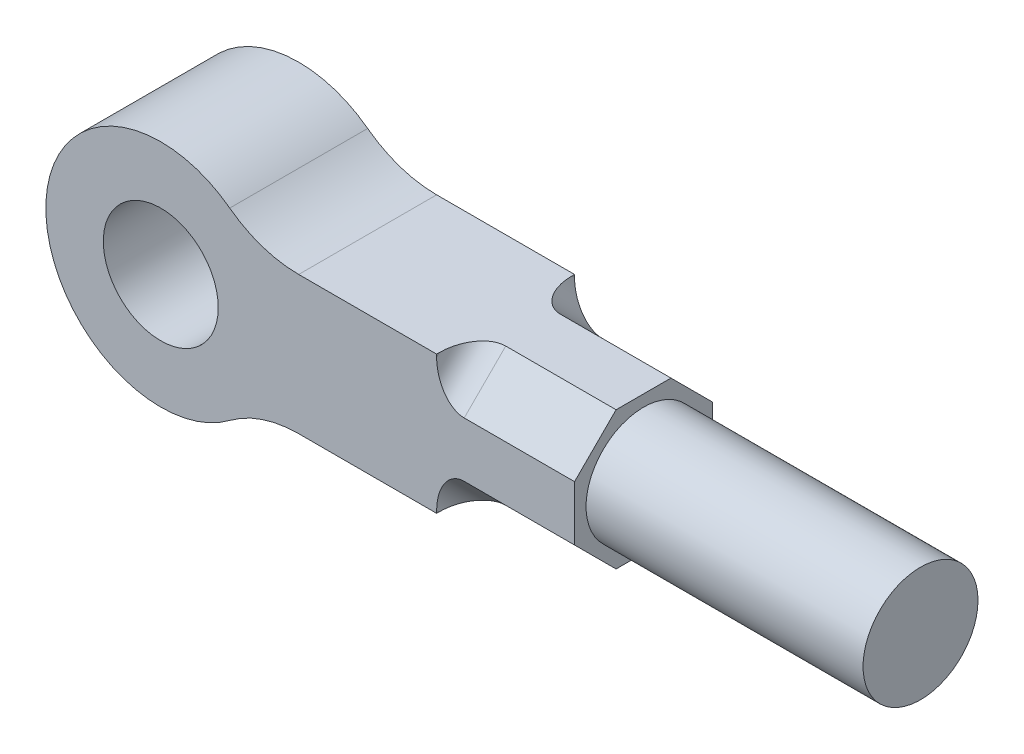
SolidWorks part; units mm, degrees
ref_plane "Front Plane" through (0, 0, 0) normal (0, 0, 1) x (1, 0, 0)
ref_plane "Top Plane" through (0, 0, 0) normal (0, 1, 0) x (1, 0, 0)
ref_plane "Right Plane" through (0, 0, 0) normal (1, 0, 0) x (0, 0, -1)
sketch "Sketch1" plane through (0, 0, 0) normal (0, 0, 1) x (1, 0, 0)
  line L0 (0, 0) -> (1046.6369, 0) construction
  line L2 (600, 300) -> (1800, 300)
  line L4 (600, -300) -> (1800, -300)
  line L5 (1800, 300) -> (1800, -300)
  arc A0 (300, 400) -> (300, -400) centre (0, 0) ccw
  circle A1 centre (0, 0) radius 250
  arc A2 (300, -400) -> (600, -300) centre (600, -800) cw
  arc A3 (300, 400) -> (600, 300) centre (600, 800) ccw
  dimension "D1" = 1000
  dimension "D2" = 500
  dimension "D4" = 500
  dimension "D3" = 600
extrude "Boss-Extrude1" add sketch "Sketch1" along normal blind 600
sketch "Sketch2" plane through (1800, 0, 0) normal (1, 0, 0) x (0, 0, -1)
  line L0 (-180.6, 300) -> (0, 119.4)
  line L1 (-600, 300) -> (0, 300) construction
  line L2 (0, -300) -> (0, 300) construction
  line L3 (0, 119.4) -> (0, 300)
  line L4 (0, 300) -> (0, 400) construction
  line L5 (0, 300) -> (-180.6, 300)
  line L6 (0, -119.4) -> (-180.6, -300)
  line L7 (-180.6, -300) -> (0, -300)
  line L8 (0, -300) -> (0, -119.4)
  line L9 (-419.4, -300) -> (-600, -119.4)
  line L10 (-600, -119.4) -> (-600, -300)
  line L11 (-600, -300) -> (-419.4, -300)
  line L12 (-600, 119.4) -> (-419.4, 300)
  line L13 (-419.4, 300) -> (-600, 300)
  line L14 (-600, 300) -> (-600, 119.4)
  circle A0 centre (-300, 0) radius 250
  point P24 (-300, 0)
  line M5 (0, -300) -> (0, 300)
  line M6 (0, 300) -> (-600, 300)
  line M7 (-600, 300) -> (-600, -300)
  line M8 (-600, -300) -> (0, -300)
  dimension "D1" = 500
  dimension "D2" = 300
  dimension "D3" = 180.6
  dimension "D4" = 180.6
  dimension "D5" = 4
extrude "Cut-Extrude1" cut sketch "Sketch2" against normal blind 600 contours L12 M7 M6 | L0 M6 M5 | L6 M5 M8 | L9 M8 M7 region at (1800, 239.8, 60.2) region at (1800, 239.8, 539.8) region at (1800, -239.8, 60.2) region at (1800, -239.8, 539.8)
extrude "Boss-Extrude2" add sketch "Sketch2<5>" along normal blind 1205 contours A0 region at (1800, 0, 300)
sketch "Sketch2<5>" plane through (1800, 0, 0) normal (1, 0, 0) x (0, 0, -1) same geometry as "Sketch2"
fillet "Fillet1" radius 120 4 edges at (1200, -209.7, 90.3) (1200, 209.7, 90.3) (1200, -209.7, 509.7) (1200, 209.7, 509.7)
